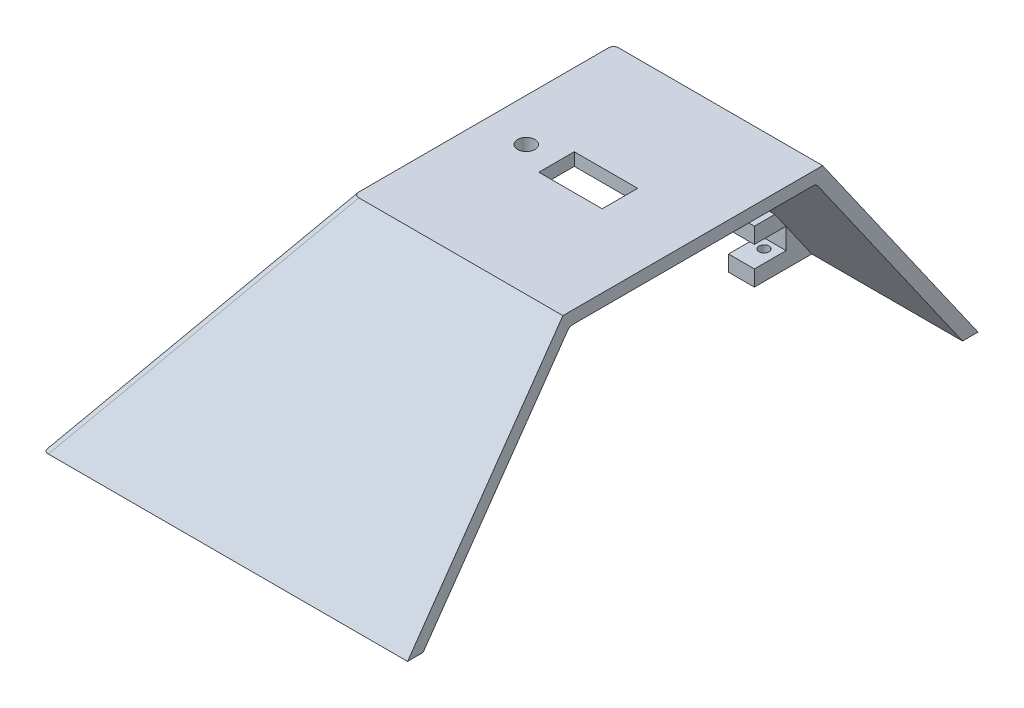
SolidWorks part; units mm, degrees
ref_plane "Alzado" through (0, 0, 0) normal (0, 0, 1) x (1, 0, 0)
ref_plane "Planta" through (0, 0, 0) normal (0, 1, 0) x (1, 0, 0)
ref_plane "Vista lateral" through (0, 0, 0) normal (1, 0, 0) x (0, 0, -1)
sketch "Croquis1" plane through (0, 0, 0) normal (0, 1, 0) x (1, 0, 0)
  line L1 (90, -90) -> (-90, -90)
  line L2 (90, -90) -> (90, 90)
  line L3 (90, 90) -> (-90, 90)
  line L4 (-90, -90) -> (-90, 90)
  line L5 (90, -90) -> (-90, 90) construction
  line L6 (90, 90) -> (-90, -90) construction
  point P0 (0, 0)
  dimension "D1" = 180
  dimension "D2" = 180
extrude "Saliente-Extruir1" add sketch "Croquis1" along normal blind 70
sketch "Croquis3" plane through (-90, 0, 0) normal (-1, 0, 0) x (0, 0, 1)
  line L0 (-90, 0) -> (-90, 70)
  line L1 (-90, 70) -> (-40.9855, 70)
  line L2 (-90, 70) -> (90, 70) construction
  line L3 (-40.9855, 70) -> (-90, 0)
  line L4 (90, 0) -> (90, 70)
  line L5 (90, 70) -> (40.9855, 70)
  line L6 (40.9855, 70) -> (90, 0)
  dimension "D1" = 35
  dimension "D2" = 35
extrude "Cortar-Extruir2" cut sketch "Croquis3" against normal up to next
sketch "Croquis2" plane through (0, 0, 90) normal (0, 0, 1) x (1, 0, 0)
  line L0 (90, 0) -> (90, 80)
  line L1 (90, 80) -> (33.9834, 80)
  line L2 (-90, 80) -> (90, 80) construction
  line L3 (33.9834, 80) -> (90, 0)
  line L4 (-90, 80) -> (-33.9834, 80)
  line L5 (-33.9834, 80) -> (-90, 0)
  line L6 (-90, 0) -> (-90, 80)
  dimension "D1" = 35
  dimension "D2" = 35
extrude "Cortar-Extruir1" cut sketch "Croquis2" against normal up to next
shell "Vaciado1" thickness 4 removed face at (0, 0, 0)
sketch "Croquis4" plane through (60.3909, 42.2862, 0) normal (0.8192, 0.5736, 0) x (0, 0, -1)
  line L0 (-90, -51.6219) -> (-40.9855, 33.8323)
  line L1 (-40.9855, 33.8323) -> (40.9855, 33.8323)
  line L2 (40.9855, 33.8323) -> (90, -51.6219)
  line L3 (90, -51.6219) -> (-90, -51.6219)
extrude "Cortar-Extruir3" cut sketch "Croquis4" against normal up to next
sketch "Croquis7" plane through (0, 0, 0) normal (0, 0, 1) x (1, 0, 0)
  line L0 (90, 0) -> (25, 0)
  line L1 (-90, 0) -> (90, 0) construction
  line L2 (25, 0) -> (25, 70)
  line L3 (40.9855, 70) -> (-40.9855, 70) construction
  line L4 (25, 70) -> (40.9855, 70)
  line L5 (40.9855, 70) -> (90, 0)
  dimension "D1" = 65
extrude "Cortar-Extruir5" cut sketch "Croquis7" against normal up to next and the other way up to next
ref_plane "Plano1" through (0, 0, 67) normal (0, 0, 1) x (1, 0, 0)
sketch "Croquis9" plane through (0, 0, 67) normal (0, 0, 1) x (1, 0, 0)
  line L0 (-85.1169, 0) -> (25, 0) construction
  line L1 (-22.5618, 0) -> (-30.7314, 0)
  line L2 (-22.5618, 0) -> (-22.5618, 16.6652)
  line L3 (-22.5618, 16.6652) -> (-30.7314, 16.6652)
  line L4 (-30.7314, 0) -> (-30.7314, 16.6652)
  line L5 (-22.5618, 0) -> (-30.7314, 16.6652) construction
  line L6 (-22.5618, 16.6652) -> (-30.7314, 0) construction
  line L7 (-26.6466, 8.3326) -> (-26.6466, -33.9407) construction
  point P4 (-26.6466, 8.3326)
extrude "Saliente-Extruir2" add sketch "Croquis9" along normal up to next
sketch "Croquis10" plane through (0, 0, 67) normal (0, 0, -1) x (-1, 0, 0)
  line L0 (22.5618, 0) -> (22.5618, 16.6652) construction
  line L1 (22.5618, 11.6729) -> (30.7314, 11.6729)
  line L2 (22.5618, 11.6729) -> (22.5618, 4.9876)
  line L3 (22.5618, 4.9876) -> (30.7314, 4.9876)
  line L4 (30.7314, 11.6729) -> (30.7314, 4.9876)
  line L5 (22.5618, 11.6729) -> (30.7314, 4.9876) construction
  line L6 (22.5618, 4.9876) -> (30.7314, 11.6729) construction
  line L7 (30.7314, 0) -> (30.7314, 16.6652) construction
  line L8 (30.7314, 8.3302) -> (22.5618, 8.3302) construction
  line L9 (30.7314, 0) -> (22.5618, 0) construction
  line L10 (30.7314, 16.6652) -> (22.5618, 16.6652) construction
  point P4 (26.6466, 8.3302)
  point P9 (0, 0)
  point P12 (26.6466, 8.3302)
  dimension "D1" = 8.335
  dimension "D2" = 8.3302
extrude "Cortar-Extruir6" cut sketch "Croquis10" against normal blind 10
sketch "Croquis11" plane through (0, 0, 0) normal (0, -1, 0) x (1, 0, 0)
  circle A0 centre (-26.5104, 74) radius 1.585
extrude "Cortar-Extruir7" cut sketch "Croquis11" against normal up to next
mirror "Simetría1" about plane through (0, 0, 0) normal (0, 0, 1) of "Cortar-Extruir6", "Saliente-Extruir2", "Cortar-Extruir7"
sketch "Croquis12" plane through (0, 70, 0) normal (0, 1, 0) x (1, 0, 0)
  line L0 (25, 40.9855) -> (-40.9855, 40.9855) construction
  line L1 (-17.9905, 5.6005) -> (2.0095, 5.6005)
  line L2 (-17.9905, 5.6005) -> (-17.9905, -5.5995)
  line L3 (-17.9905, -5.5995) -> (2.0095, -5.5995)
  line L4 (2.0095, 5.6005) -> (2.0095, -5.5995)
  line L5 (-17.9905, 5.6005) -> (2.0095, -5.5995) construction
  line L6 (-17.9905, -5.5995) -> (2.0095, 5.6005) construction
  line L8 (-40.9855, 40.9855) -> (-40.9855, -40.9855) construction
  point P4 (-7.9905, 0.0005)
  dimension "D1" = 11.2
  dimension "D2" = 20
  dimension "D3" = 40.985
  dimension "D4" = 32.995
extrude "Cortar-Extruir8" cut sketch "Croquis12" against normal up to next
fillet "Redondeo1" radius 2 7 edges at (-6.9516, 66, -38.9032) (-6.9516, 66, 38.9032) (-65.4927, 35, 65.4927) (-38.9032, 66, 0) (-62.0101, 33, -62.0101) (-65.4927, 35, -65.4927) (-62.0101, 33, 62.0101)
sketch "Croquis13" plane through (0, 70, 0) normal (0, 1, 0) x (1, 0, 0)
  circle A0 centre (-27.5466, 0) radius 2.75
  dimension "D1" = 5.5
extrude "Cortar-Extruir9" cut sketch "Croquis13" against normal up to next
